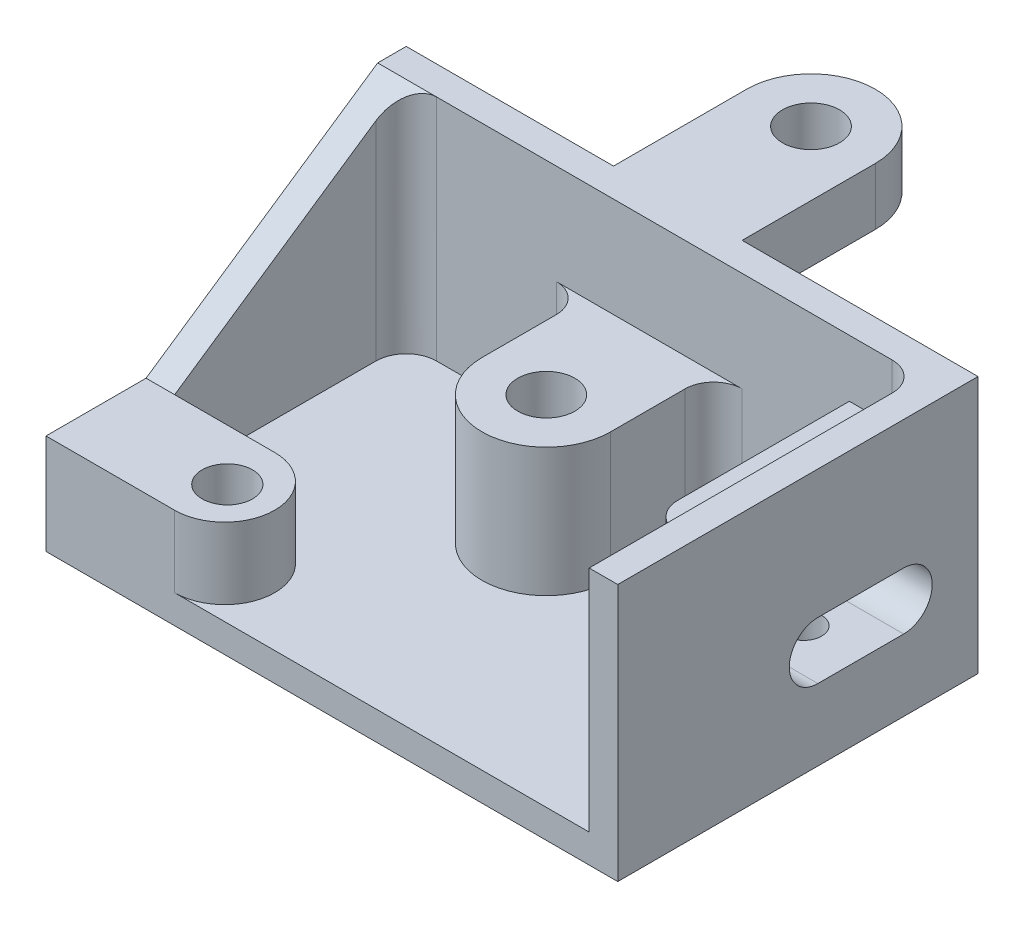
SolidWorks part; units mm, degrees
ref_plane "Front Plane" through (0, 0, 0) normal (0, 0, 1) x (1, 0, 0)
ref_plane "Top Plane" through (0, 0, 0) normal (0, 1, 0) x (1, 0, 0)
ref_plane "Right Plane" through (0, 0, 0) normal (1, 0, 0) x (0, 0, -1)
sketch "Sketch1" plane through (0, 0, 0) normal (0, 1, 0) x (1, 0, 0)
  line L0 (60.325, -28.3469) -> (60.325, -50.8)
  line L1 (-60.325, 29.2182) -> (66.675, 29.2182)
  line L2 (-60.325, 29.2182) -> (-60.325, -50.8)
  line L3 (-47.625, -50.8) -> (66.675, -50.8)
  line L4 (66.675, 29.2182) -> (66.675, -50.8)
  line L5 (20.6375, 22.8682) -> (53.975, 22.8682)
  line L6 (-53.975, 16.1031) -> (-53.975, -44.45)
  line L7 (-14.2875, 0) -> (-14.2875, 16.5182)
  line L8 (14.2875, 0) -> (14.2875, 16.5182)
  line L9 (44.45, 22.8682) -> (44.45, -15.2318)
  line L10 (50.8, -21.5818) -> (53.5599, -21.5818)
  line L11 (-53.975, 22.8682) -> (60.325, 22.8682) construction
  line L12 (60.325, 22.8682) -> (60.325, -50.8) construction
  line L13 (-47.2099, 22.8682) -> (-20.6375, 22.8682)
  line L14 (-20.6375, 22.8682) -> (20.6375, 22.8682)
  line L15 (-53.975, 22.8682) -> (-53.975, -50.8) construction
  line L16 (-53.975, -44.45) -> (-53.975, -50.8)
  line L17 (-60.325, -50.8) -> (-47.625, -50.8)
  line L18 (60.325, -28.3469) -> (60.325, 16.5182)
  circle A0 centre (0, 0) radius 6.35 construction
  arc A1 (-14.2875, 0) -> (14.2875, 0) centre (0, 0) ccw
  arc A2 (14.2875, 16.5182) -> (20.6375, 22.8682) centre (20.6375, 16.5182) cw
  arc A3 (44.45, -15.2318) -> (50.8, -21.5818) centre (50.8, -15.2318) ccw
  arc A4 (53.5599, -21.5818) -> (60.325, -28.3469) centre (53.5599, -28.3469) cw
  arc A5 (-20.6375, 22.8682) -> (-14.2875, 16.5182) centre (-20.6375, 16.5182) cw
  arc A6 (60.325, 16.5182) -> (53.975, 22.8682) centre (53.975, 16.5182) ccw
  arc A8 (-53.975, 16.1031) -> (-47.2099, 22.8682) centre (-47.2099, 16.1031) cw
  point P11 (0, 0)
  point P30 (0, 0)
  point P34 (58.3435, -23.5632)
  dimension "D1" = 12.7
  dimension "D7" = 28.575
  dimension "D10" = 6.35
  dimension "D11" = 6.35
  dimension "D2" = 6.35
  dimension "D13" = 6.7651
  dimension "D14" = 6.35
  dimension "D3" = 50.8
  dimension "D4" = 60.325
  dimension "D5" = 127
  dimension "D8" = 22.225
  dimension "D9" = 50.8
  dimension "D15" = 6.7651
  dimension "D16" = 6.35
  dimension "D18" = 127
  dimension "D6" = 6.35
extrude "Boss-Extrude1" add sketch "Sketch1" along normal blind 6.35 contours L6 A8 L13 L14 L5 A6 L18 L0 L3 L4 L1 L2 L17 L16 | A8 L6 L16 L17 L3 L0 A4 L10 A3 L9 L5 A2 L8 A1 L7 A5 L13 | L14 A5 L7 A1 L8 A2 | L18 A6 L5 L9 A3 L10 A4 region at (61.8261, 0, 5.9143) region at (52.4779, 0, -0.3093) region at (-1.4746, 0, 18.4896) region at (0, 0, -5.9497)
extrude "Boss-Extrude2" add sketch "Sketch1<4>" along normal blind 57.15 contours L6 A8 L13 L14 L5 A6 L18 L0 L3 L4 L1 L2 L17 L16 region at (61.8261, 0, 5.9143)
sketch "Sketch1<4>" plane through (0, 0, 0) normal (0, 1, 0) x (1, 0, 0) same geometry as "Sketch1"
extrude "Boss-Extrude3" add sketch "Sketch1<5>" along normal blind 44.45 contours L18 A6 L5 L9 A3 L10 A4 region at (52.4779, 0, -0.3093)
sketch "Sketch1<5>" plane through (0, 0, 0) normal (0, 1, 0) x (1, 0, 0) same geometry as "Sketch1"
extrude "Boss-Extrude4" add sketch "Sketch1<6>" along normal blind 34.925 contours L14 A5 L7 A1 L8 A2 region at (0, 0, -5.9497)
sketch "Sketch1<6>" plane through (0, 0, 0) normal (0, 1, 0) x (1, 0, 0) same geometry as "Sketch1"
sketch "Sketch4" plane through (0, 57.15, 0) normal (0, 1, 0) x (1, 0, 0)
  line L0 (-14.2875, 58.801) -> (-14.2875, 29.2182)
  line L1 (-60.325, 29.2182) -> (66.675, 29.2182) construction
  line L2 (14.2875, 58.801) -> (14.2875, 29.2182)
  line L3 (-14.2875, 16.5182) -> (-14.2875, 0) construction
  line L4 (14.2875, 16.5182) -> (14.2875, 0) construction
  line L5 (-14.2875, 29.2182) -> (14.2875, 29.2182)
  circle A0 centre (0, 58.801) radius 14.2875
  arc A1 (-14.2875, 0) -> (14.2875, 0) centre (0, 0) ccw construction
  circle A2 centre (0, 58.801) radius 6.35
  line M10 (66.675, 29.2182) -> (-60.325, 29.2182)
  dimension "D2" = 12.7
  dimension "D1" = 58.801
extrude "Boss-Extrude5" add sketch "Sketch4" against normal blind 12.7 contours A0 L0 L2 M10 | A0 A2 region at (0, 57.15, -38.6758) region at (0, 57.15, -72.6844)
sketch "Sketch5" plane through (-60.325, 0, 0) normal (-1, 0, 0) x (0, 0, 1)
  line L0 (-22.8682, 57.15) -> (28.575, 22.225)
  line L1 (-29.2182, 57.15) -> (50.8, 57.15) construction
  line L2 (28.575, 22.225) -> (50.8, 22.225)
  line L3 (50.8, 57.15) -> (50.8, 0) construction
  line L4 (50.8, 22.225) -> (50.8, 57.15)
  line L5 (50.8, 57.15) -> (-22.8682, 57.15)
  line L6 (-29.2182, 0) -> (50.8, 0) construction
  line L7 (-22.8682, 57.15) -> (-22.8682, 6.35) construction
  point P12 (0, 0)
  point P13 (0, 0)
  dimension "D1" = 22.225
  dimension "D2" = 22.225
extrude "Cut-Extrude1" cut sketch "Sketch5" against normal up to next
sketch "Sketch6" plane through (0, 6.35, 0) normal (0, 1, 0) x (1, 0, 0)
  line L0 (-31.75, -28.575) -> (-53.975, -28.575)
  line L1 (-53.975, -28.575) -> (-53.975, -50.8) construction
  line L2 (-53.975, -28.575) -> (-60.325, -28.575) construction
  line L3 (-53.975, -50.8) -> (60.325, -50.8) construction
  line L4 (-53.975, -50.8) -> (-31.75, -50.8)
  line L5 (-60.325, -28.575) -> (-60.325, -50.8) construction
  line L6 (-53.975, -28.575) -> (-53.975, -50.8)
  arc A0 (-31.75, -50.8) -> (-31.75, -28.575) centre (-31.75, -39.6875) ccw
  point P6 (0, 0)
  point P11 (0, 0)
  dimension "D1" = 28.575
extrude "Boss-Extrude6" add sketch "Sketch6" along normal up to surface (15.875 mm away) up to face at (-57.15, 22.225, 39.6875)
hole_wizard "CBORE for M5 Cross Recess Pan Head Screw1" positions "Sketch12" profile "Sketch11" counterbore size "M5" standard "IS" end condition through all
sketch "Sketch12" plane through (0, 0, 0) normal (0, -1, 0) x (-1, 0, 0)
  point P0 (30.8732, -39.9735)
sketch "Sketch11" plane through (-30.8732, 0, 39.9735) normal (1, 0, 0) x (0, 0, -1)
  line L0 (0, 0) -> (0, 57.15)
  line L1 (0, 57.15) -> (5.6007, 57.15)
  line L3 (5.6007, 57.15) -> (5.6007, 3.175)
  line L4 (5.6007, 3.175) -> (7.9375, 3.175)
  line L5 (7.9375, 3.175) -> (7.9375, 0)
  line L7 (7.9375, 0) -> (0, 0)
  line L11 (0, -6.35) -> (0, 107.95) construction
  dimension "Thru Hole Dia." = 11.2014
  dimension "Thru Hole Depth" = 57.15
  dimension "C'Bore Dia." = 15.875
  dimension "C'Bore Depth" = 3.175
hole_wizard "CBORE for M5 Cross Recess Pan Head Screw2" positions "Sketch15" profile "Sketch14" counterbore size "M5" standard "IS" end condition up to next
sketch "Sketch15" plane through (0, 0, 0) normal (0, -1, 0) x (-1, 0, 0)
  point P0 (0, 0)
sketch "Sketch14" plane through (0, 0, 0) normal (1, 0, 0) x (0, 0, -1)
  line L0 (0, 0) -> (0, 34.925)
  line L1 (0, 34.925) -> (6.35, 34.925)
  line L3 (6.35, 34.925) -> (6.35, 3.175)
  line L4 (6.35, 3.175) -> (11.1125, 3.175)
  line L5 (11.1125, 3.175) -> (11.1125, 0)
  line L7 (11.1125, 0) -> (0, 0)
  line L11 (0, -6.35) -> (0, 107.95) construction
  dimension "Thru Hole Dia." = 12.7
  dimension "Thru Hole Depth" = 34.925
  dimension "C'Bore Dia." = 22.225
  dimension "C'Bore Depth" = 3.175
sketch "Sketch16" plane through (66.675, 0, 0) normal (1, 0, 0) x (0, 0, -1)
  line L0 (-6.35, 22.225) -> (12.7, 22.225) construction
  line L1 (-6.35, 28.575) -> (12.7, 28.575)
  line L2 (-6.35, 15.875) -> (12.7, 15.875)
  line L3 (29.2182, 0) -> (-50.8, 0) construction
  line L5 (-50.8, 57.15) -> (-50.8, 0) construction
  arc A0 (-6.35, 28.575) -> (-6.35, 15.875) centre (-6.35, 22.225) ccw
  arc A1 (12.7, 15.875) -> (12.7, 28.575) centre (12.7, 22.225) ccw
  point P2 (3.175, 22.225)
  dimension "D3" = 6.35
  dimension "D1" = 22.225
  dimension "D2" = 19.05
  dimension "D4" = 44.45
extrude "Cut-Extrude3" cut sketch "Sketch16" against normal up to next
sketch "Sketch18" plane through (0, 0, 0) normal (0, -1, 0) x (-1, 0, 0)
  line L0 (-66.675, 29.2182) -> (-66.675, -50.8) construction
  line L1 (60.325, -50.8) -> (-66.675, -50.8) construction
  circle A0 centre (-53.975, 3.175) radius 4.0005
  dimension "D1" = 8.001
  dimension "D2" = 12.7
  dimension "D3" = 53.975
extrude "Cut-Extrude4" cut sketch "Sketch18" against normal up to next
